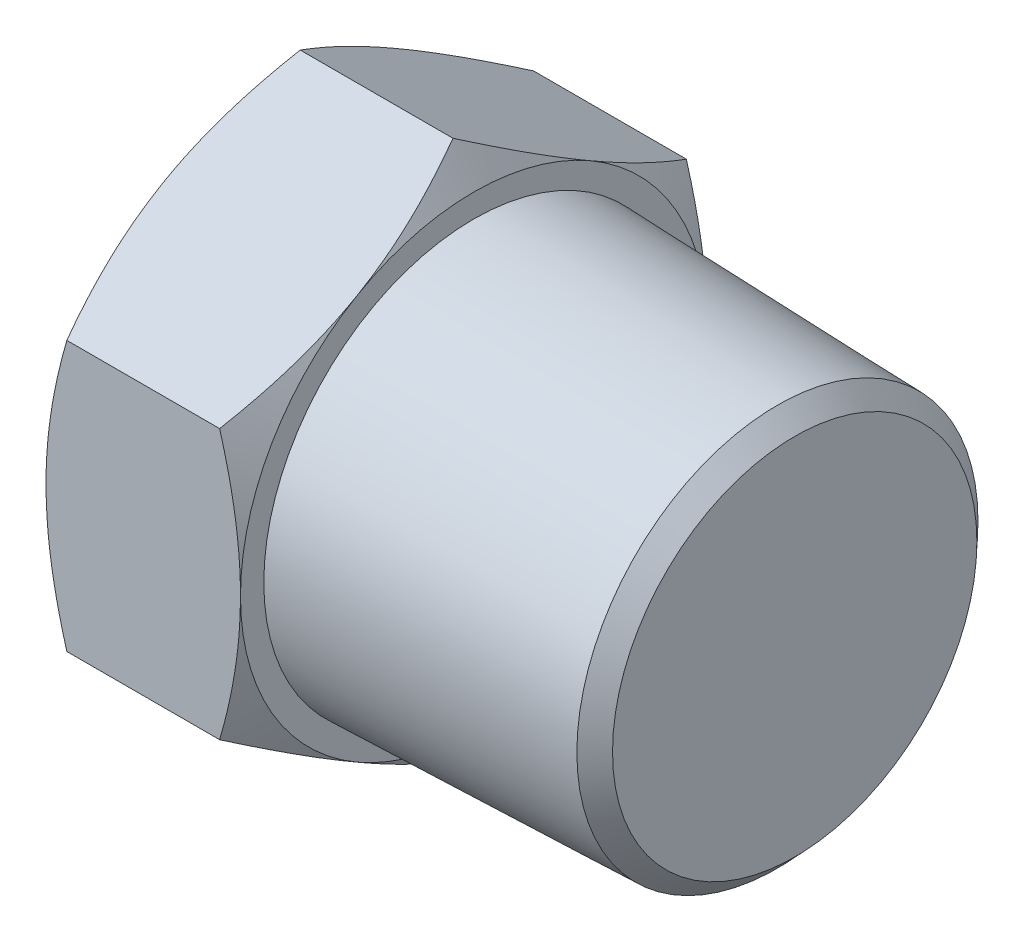
SolidWorks part; units mm, degrees
ref_plane "Front Plane" through (0, 0, 0) normal (0, 0, 1) x (1, 0, 0)
ref_plane "Top Plane" through (0, 0, 0) normal (0, 1, 0) x (1, 0, 0)
ref_plane "Right Plane" through (0, 0, 0) normal (1, 0, 0) x (0, 0, -1)
sketch "Sketch1" plane through (0, 0, 0) normal (0, 0, 1) x (1, 0, 0)
  line L0 (-10.5172, 0) -> (10.5172, 0) construction
  line L1 (-10.5172, 9.525) -> (-10.5172, -9.525) construction
  line L2 (-2.5797, 8.5725) -> (-2.5797, -8.5725) construction
  line L3 (4.8727, -8.3405) -> (10.5172, -8.1647) construction
  line L4 (-2.5797, 8.5725) -> (10.5172, 8.1647) construction
  line L5 (10.5172, 8.1647) -> (10.5172, -8.1647) construction
  point P7 (-2.5797, 0)
  point P8 (4.8727, -8.3405)
  dimension "B" = 19.05
  dimension "D3" = 1.783
  dimension "D1" = 5.6444
  dimension "D2" = 1.783
ref_plane "Plane1" through (10.5172, 0, 0) normal (1, 0, 0) x (0, 0, -1)
sketch "Sketch2" plane through (10.5172, 0, 0) normal (1, 0, 0) x (0, 0, -1)
  circle A0 centre (0, 0) radius 8.1647
extrude "Extrude1" add sketch "Sketch2" against normal up to vertex (13.0969 mm away) draft 1.783 up to point (-2.5797, 0, 0) draft outward yes
sketch "Sketch6" plane through (-2.5797, 0, 0) normal (-1, 0, 0) x (0, 0, 1)
  line L1 (0, 10.9985) -> (-9.525, 5.4993)
  line L2 (-9.525, 5.4993) -> (-9.525, -5.4993)
  line L3 (-9.525, -5.4993) -> (0, -10.9985)
  line L4 (0, -10.9985) -> (9.525, -5.4993)
  line L5 (9.525, -5.4993) -> (9.525, 5.4993)
  line L6 (9.525, 5.4993) -> (0, 10.9985)
  circle A0 centre (0, 0) radius 9.525 construction
extrude "Extrude2" add sketch "Sketch6" along normal up to vertex (7.9375 mm away) separate body up to point (-10.5172, 0, 0)
sketch "Sketch7" plane through (-10.5172, 0, 0) normal (-1, 0, 0) x (0, 0, 1)
  circle A0 centre (0, 0) radius 9.525 construction
  circle A1 centre (0, 0) radius 9.525
extrude "Cut-Extrude1" cut sketch "Sketch7" against normal through all draft 60 flip side to cut
sketch "Sketch8" plane through (-2.5797, 0, 0) normal (1, 0, 0) x (0, 0, -1)
  circle A0 centre (0, 0) radius 9.525 construction
  circle A1 centre (0, 0) radius 9.525
extrude "Cut-Extrude2" cut sketch "Sketch8" against normal through all draft 60 flip side to cut
chamfer "Chamfer1" distance 0.7056 angle 45 1 edges at (10.5172, 0, -8.1647) first distance on face at (-2.5797, 0, -8.5725)
sketch "Sketch4" [suppressed] plane through (10.5172, 0, 0) normal (1, 0, 0) x (0, 0, -1)
  circle A1 centre (0, 0) radius 8.1647
  circle A2 centre (0, 0) radius 8.1647
  point P0 (0, 8.1647)
  dimension "D1" = 0
curve "Helix/Spiral1" [suppressed] parameters "Pitch"=1.4111
sketch "Sketch5" [suppressed] plane through (0, 0, 0) normal (0, 0, 1) x (1, 0, 0)
  line L0 (10.429, 8.3175) -> (11.8401, 8.3175) construction
  line L1 (11.8401, 8.3175) -> (11.1345, 7.0954) construction
  line L2 (11.1345, 7.0954) -> (10.429, 8.3175) construction
  line L3 (10.5172, 8.1647) -> (11.7519, 8.1647) construction
  line L4 (11.0464, 7.2482) -> (11.2227, 7.2482)
  line L5 (11.1345, 7.2482) -> (11.1345, 7.0954) construction
  line L6 (11.1345, 8.1647) -> (11.1345, 8.3175) construction
  line L7 (11.1345, 8.2411) -> (10.4731, 8.2411) construction
  line L8 (10.4731, 8.2411) -> (11.7519, 8.1647)
  line L9 (11.2227, 7.2482) -> (11.7519, 8.1647)
  line L10 (11.0464, 7.2482) -> (10.4731, 8.2411)
  dimension "D1" = 1.4111
  dimension "D2" = 0.1764
  dimension "D3" = 60
sweep "Cut-Sweep1" [suppressed] cut profiles "Sketch5" path "Helix/Spiral1"
combine bodies "Combine1" [suppressed] operation type add bodies to combine 106 102
ref_plane "Contact Plane 1" through (-2.3257, 0, 0) normal (1, 0, 0) x (0, 0, -1)
ref_plane "Contact Plane 2" through (10.5172, 0, 0) normal (1, 0, 0) x (0, 0, -1)
ref_axis "Center Axis 1" through (-2.5797, 0, 0) along (1, 0, 0)
equation "\"D1@Chamfer1\" = \"Pitch@Helix/Spiral1\"*.5"
equation "\"D3@Helix/Spiral1\" = \"A@Sketch1\""
equation "\"D1@Sketch1\" = \"Pitch@Helix/Spiral1\"*4"
equation "\"D1@Sketch5\"=\"Pitch@Helix/Spiral1\""
equation "\"D2@Sketch5\"=\"Pitch@Helix/Spiral1\"*.125"
